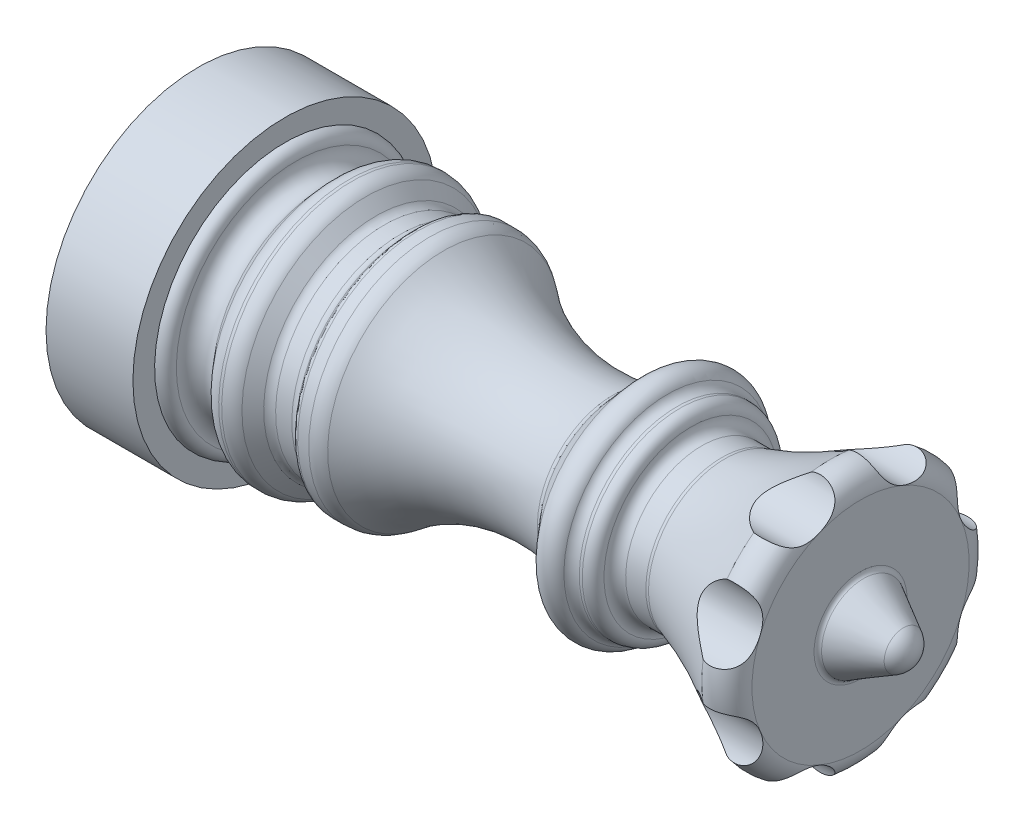
SolidWorks part; units mm, degrees
material "Latão"
ref_plane "Plano frontal" through (0, 0, 0) normal (0, 0, 1) x (1, 0, 0)
ref_plane "Plano superior" through (0, 0, 0) normal (0, 1, 0) x (1, 0, 0)
ref_plane "Plano direito" through (0, 0, 0) normal (1, 0, 0) x (0, 0, -1)
sketch "Esboço1" plane through (0, 0, 0) normal (0, 0, 1) x (1, 0, 0)
  line L0 (0, 0) -> (0, 6)
  line L1 (0, 0) -> (30, 0)
  line L2 (0, 0) -> (0, 6) construction
  line L3 (0, 6) -> (30, 6) construction
  line L4 (30, 0) -> (30, 6) construction
  line L5 (2.7283, 5.0408) -> (3.308, 5.7077)
  line L6 (5.3429, 5) -> (6.5429, 5)
  line L7 (6.5429, 5) -> (7.0404, 5.5723)
  line L8 (7.0404, 5.5723) -> (8.0404, 5.5723)
  line L9 (16.2451, 3.5) -> (17.4621, 4.9)
  line L10 (18.6879, 4.5) -> (19.6879, 4.5)
  line L11 (19.6879, 4.5) -> (19.6879, 3.5)
  line L12 (19.6879, 3.5) -> (21.1879, 3.5)
  line L13 (3.9495, 6) -> (4.0862, 6)
  line L14 (27.5, 5) -> (27.5, 1.9933)
  line L15 (0, 6) -> (1, 6)
  line L16 (5.3429, 5) -> (5.3429, 3.8472) construction
  line L17 (5.3429, 5) -> (4.7277, 5.7077)
  line L18 (1.5, 5.5) -> (1.5, 7.2448) construction
  line L19 (27.5, 1.9933) -> (29.4774, 0.89)
  arc A0 (1, 6) -> (1.5, 5.5) centre (1, 5.5) cw
  arc A1 (4.0862, 6) -> (4.7277, 5.7077) centre (4.0862, 5.15) cw
  arc A2 (1.5, 5.5) -> (2.7283, 5.0408) centre (2.2, 5.5) ccw
  arc A3 (30, 0) -> (29.4774, 0.89) centre (28.9808, 0) ccw
  arc A4 (26.1038, 5.9182) -> (21.1879, 3.5) centre (16.6693, 18.8919) cw
  arc A5 (3.9495, 6) -> (3.308, 5.7077) centre (3.9495, 5.15) ccw
  arc A6 (8.0404, 5.5723) -> (16.2451, 3.5) centre (14.0981, 12.2777) ccw
  arc A7 (17.4621, 4.9) -> (18.6879, 4.5) centre (17.9904, 4.4408) cw
  arc A8 (26.1038, 5.9182) -> (27.5, 5) centre (26.5, 5) cw
  dimension "D3" = 0.85
  dimension "D5" = 1
  dimension "D7" = 3.5
  dimension "D12" = 1.2
  dimension "D10" = 0.7
  dimension "D15" = 3.5
  dimension "D18" = 1
  dimension "D19" = 1
  dimension "D22" = 0.7
  dimension "D24" = 1
  dimension "D8" = 82
  dimension "D13" = 5
  dimension "D14" = 0.4
  dimension "D16" = 2.5
  dimension "D9" = 0.5
  dimension "D1" = 6
  dimension "D2" = 30
  dimension "D4" = 41
  dimension "D6" = 1.5
  dimension "D17" = 29.159
  dimension "D27" = 1
revolve "Revolução1" add sketch "Esboço1" angle 360 about L1 region at (13.6682, 2.3539, 0)
ref_axis "Eixo3" through (38.9105, 0, 0) along (-1, 0, 0)
fillet "Filete2" radius 0.5 1 edges at (19.6879, 0, 4.5)
fillet "Filete3" radius 0.5 6 edges at (6.5429, 0, 5) (5.3429, 0, 5) (16.2451, 0, 3.5) (18.6879, 0, 4.5) (19.6879, 0, 3.5) (21.1879, 0, 3.5)
sketch "Esboço2" plane through (27.5, 0, 0) normal (1, 0, 0) x (0, 0, -1)
  circle A0 centre (-6.75, 0) radius 1.75
  dimension "D1" = 3.5
  dimension "D2" = 6.75
extrude "Corte-extrusão1" cut sketch "Esboço2" against normal blind 5
pattern_circular "PadrãoCircular1" count 8 over 360 about axis through (38.9105, 0, 0) along (-1, 0, 0) of "Corte-extrusão1"
fillet "Filete4" radius 0.25 2 edges at (7.0404, 0, 5.5723) (27.5, 0, 1.9933)
fillet "Filete5" radius 1 1 edges at (8.0404, 0, 5.5723)
move or copy body "Corpo-Mover/Copiar1" bodies to move or copy 110 copy no rotation origin (0, 0, 0) rotation axis (-1, 0, 0) rotation angle 22.5
chamfer "Chanfro1" distance 0.35 angle 45 1 edges at (0, 2.2961, 5.5433)
sketch "Sketch1" plane through (0, 0, 0) normal (-1, 0, 0) x (0, 0, 1)
  circle A0 centre (0, 0) radius 7
  dimension "D1" = 14
extrude "Boss-Extrude1" add sketch "Sketch1" against normal blind 1
extrude "Boss-Extrude2" add sketch "Sketch1<2>" along normal blind 3
sketch "Sketch1<2>" plane through (0, 0, 0) normal (-1, 0, 0) x (0, 0, 1) same geometry as "Sketch1"
sketch "Sketch2" plane through (-3, 0, 0) normal (-1, 0, 0) x (0, 0, 1)
  circle A0 centre (0, 0) radius 6.05
  dimension "D1" = 12.1
extrude "Cut-Extrude1" cut sketch "Sketch2" against normal blind 3.2
